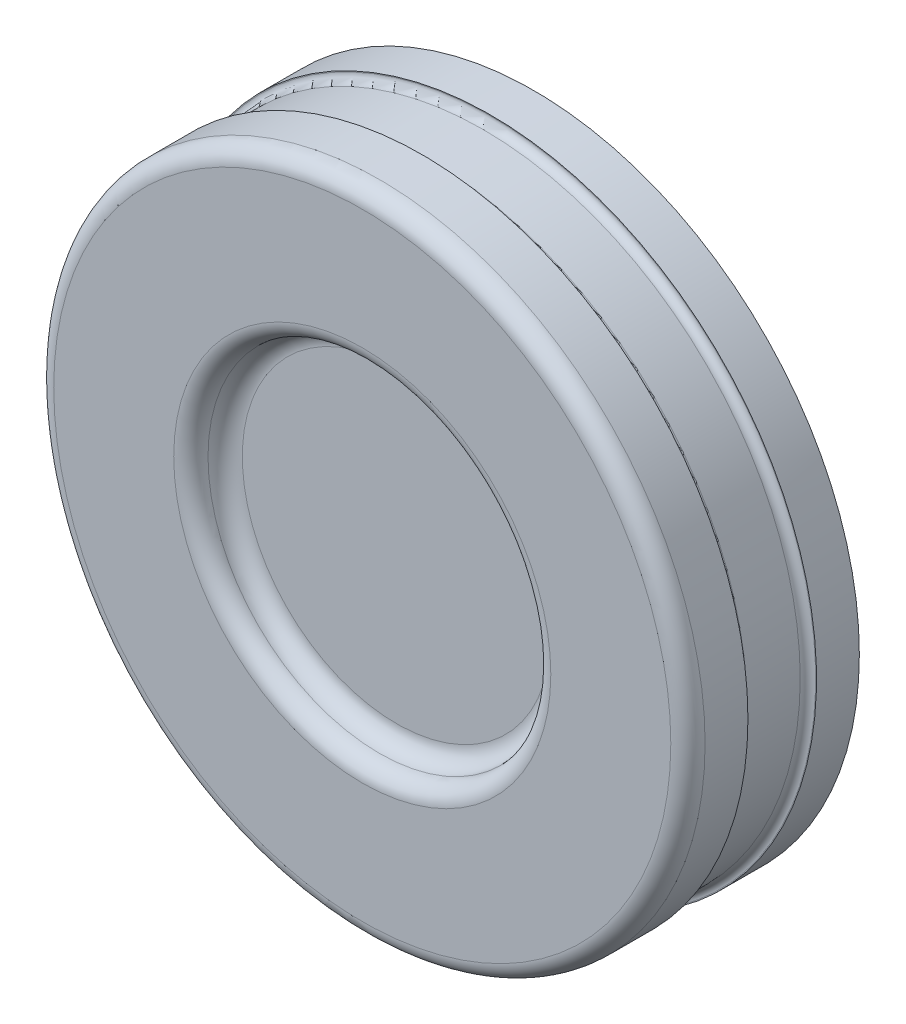
SolidWorks part; units mm, degrees
ref_plane "Front Plane" through (0, 0, 0) normal (0, 0, 1) x (1, 0, 0)
ref_plane "Top Plane" through (0, 0, 0) normal (0, 1, 0) x (1, 0, 0)
ref_plane "Right Plane" through (0, 0, 0) normal (1, 0, 0) x (0, 0, -1)
sketch "Sketch1" plane through (0, 0, 0) normal (0, 0, 1) x (1, 0, 0)
  circle A0 centre (0, 0) radius 19
  dimension "D1" = 38
extrude "Boss-Extrude1" add sketch "Sketch1" along normal blind 10
sketch "Sketch2" plane through (0, 0, 10) normal (0, 0, 1) x (1, 0, 0)
  circle A0 centre (0, 0) radius 10
  dimension "D1" = 20
extrude "Cut-Extrude1" cut sketch "Sketch2" against normal blind 2
fillet "Fillet1" radius 1 3 edges at (10, 0, 8) (10, 0, 10) (19, 0, 10)
sketch "Sketch3" plane through (0, 0, 0) normal (0, 1, 0) x (1, 0, 0)
  line L0 (-19, 0) -> (-19, -9) construction
  line L1 (-19.5, -2.5) -> (-18.5, -2.5)
  line L2 (-19.5, -2.5) -> (-19.5, -6.5)
  line L3 (-19.5, -6.5) -> (-18.5, -6.5)
  line L4 (-18.5, -2.5) -> (-18.5, -6.5)
  line L5 (-19.5, -2.5) -> (-18.5, -6.5) construction
  line L6 (-19.5, -6.5) -> (-18.5, -2.5) construction
  line L7 (0, 0) -> (0, -50000) construction
  point P0 (-19, -4.5)
  dimension "D1" = 4
  dimension "D2" = 1
revolve "Cut-Revolve1" cut sketch "Sketch3" angle 360 about L7
fillet "Fillet2" radius 0.45 2 edges at (-18.5, 0, 6.5) (-18.5, 0, 2.5)
